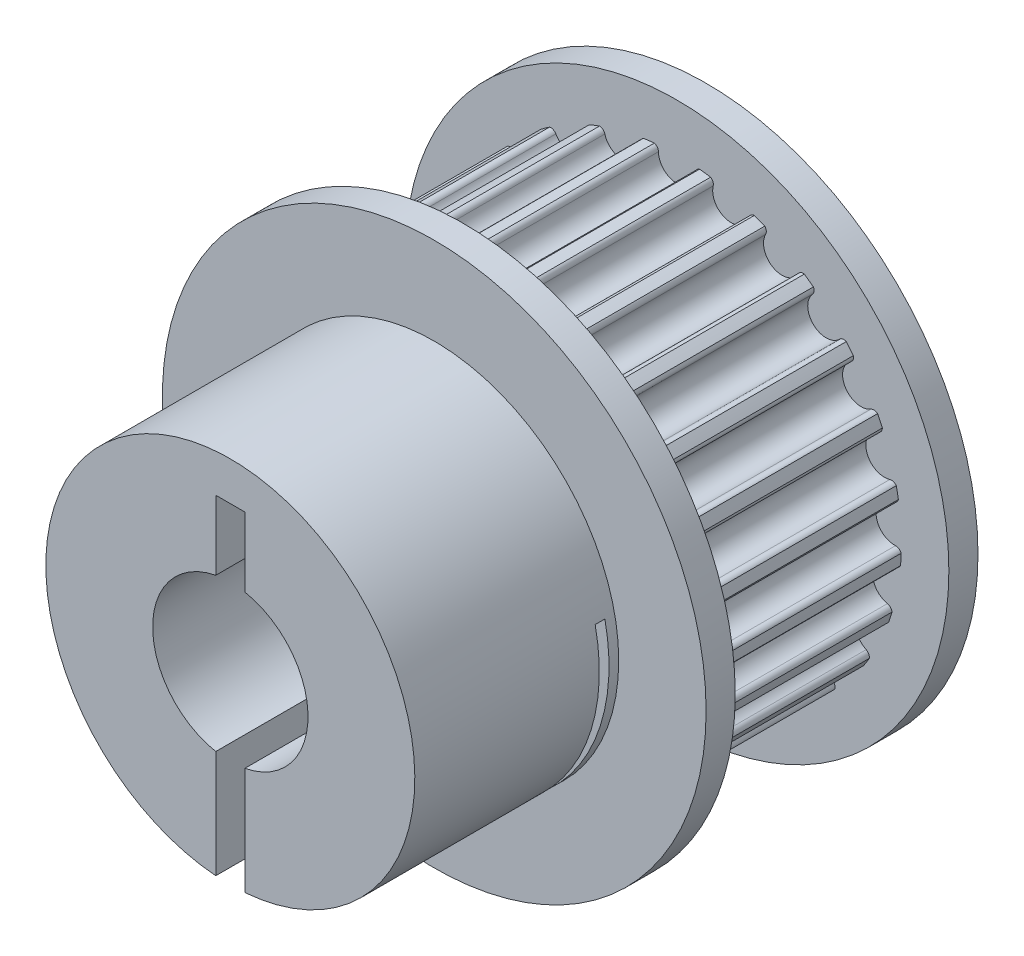
SolidWorks part; units mm, degrees
material "6061 合金"
ref_plane "前基準面" through (0, 0, 0) normal (0, 0, 1) x (1, 0, 0)
ref_plane "上基準面" through (0, 0, 0) normal (0, 1, 0) x (1, 0, 0)
ref_plane "右基準面" through (0, 0, 0) normal (1, 0, 0) x (0, 0, -1)
sketch "草圖1" plane through (0, 0, 0) normal (0, 0, 1) x (1, 0, 0)
  circle A0 centre (0, 0) radius 11.555
  dimension "D1" = 23.11
extrude "填料-伸長1" add sketch "草圖1" along normal blind 11
sketch "草圖2" plane through (0, 0, 11) normal (0, 0, 1) x (1, 0, 0)
  line L0 (-1.4082, 11.4689) -> (0, 0) construction
  line L1 (0, 0) -> (1.4082, 11.4689) construction
  arc A0 (-1.4082, 11.4689) -> (1.4082, 11.4689) centre (0, 0) cw
  circle A1 centre (0, 0) radius 11.555 construction
  arc A2 (-0.955, 11.2155) -> (0.955, 11.2155) centre (0, 11.2301) ccw
  arc A3 (-1.4082, 11.4689) -> (-0.955, 11.2155) centre (-1.255, 11.211) cw
  arc A4 (1.4082, 11.4689) -> (0.955, 11.2155) centre (1.255, 11.211) ccw
  point P6 (0, 11.555)
  point P11 (0, 10.275)
  dimension "D2" = 1.91
  dimension "D4" = 0.3
  dimension "D1" = 1.28
  dimension "D3" = 14
extrude "除料-伸長1" cut sketch "草圖2" against normal up to next contours A4 A0 A3 A2 region at (0, 10.9973, 11)
pattern_circular "環狀複製排列1" count 25 over 360 about axis through (0, 0, 11) along (0, 0, 1) of "除料-伸長1"
sketch "草圖3" plane through (0, 0, 11) normal (0, 0, 1) x (1, 0, 0)
  circle A0 centre (0, 0) radius 14
  dimension "D1" = 28
extrude "填料-伸長2" add sketch "草圖3" along normal blind 1.5
ref_plane "平面1" through (0, 0, 5.5) normal (0, 0, -1) x (-1, 0, 0)
mirror "鏡射1" about plane through (0, 0, 5.5) normal (0, 0, -1) of "填料-伸長2"
sketch "草圖4" plane through (0, 0, 12.5) normal (0, 0, 1) x (1, 0, 0)
  circle A0 centre (0, 0) radius 9.5
  dimension "D1" = 19
extrude "填料-伸長3" add sketch "草圖4" along normal blind 10.5
sketch "草圖5" plane through (0, 0, 23) normal (0, 0, 1) x (1, 0, 0)
  line L0 (-9.2871, 2) -> (9.2871, 2)
  arc A0 (9.2871, 2) -> (-9.2871, 2) centre (0, 0) cw
  circle A1 centre (0, 0) radius 9.5 construction
  dimension "D1" = 2
extrude "除料-伸長2" cut sketch "草圖5" against normal blind 0.5 from offset 9.5 offset against normal yes
sketch "草圖6" plane through (0, 0, 23) normal (0, 0, 1) x (1, 0, 0)
  circle A0 centre (0, 0) radius 4
  dimension "D1" = 8
extrude "除料-伸長3" cut sketch "草圖6" against normal up to next
sketch "草圖7" plane through (0, 0, 23) normal (0, 0, 1) x (1, 0, 0)
  line L0 (-0.75, -3.9291) -> (-0.75, -9.4703)
  line L1 (0.75, -3.9291) -> (0.75, -9.4703)
  arc A0 (0.75, -9.4703) -> (-0.75, -9.4703) centre (0, 0) cw
  circle A1 centre (0, 0) radius 9.5 construction
  arc A2 (-0.75, -3.9291) -> (0.75, -3.9291) centre (0, 0) ccw
  circle A3 centre (0, 0) radius 4 construction
  point P10 (0, -4)
  point P11 (0, -9.5)
  dimension "D1" = 1.5
extrude "除料-伸長4" cut sketch "草圖7" against normal up to next
sketch "草圖8" plane through (0, 0, 0) normal (1, 0, 0) x (0, 0, -1)
  line L0 (-23, 7.5) -> (-18.5, 3.5)
  line L1 (-18.5, 3.5) -> (-23, 3.5)
  line L2 (-23, 3.5) -> (-23, 7.5)
  line L3 (-23, -9.4703) -> (-23, -3.9291) construction
  dimension "D1" = 4.5
  dimension "D2" = 2
  dimension "D3" = 4
extrude "除料-伸長6" cut sketch "草圖8" against normal blind 0.75 and the other way blind 0.75
